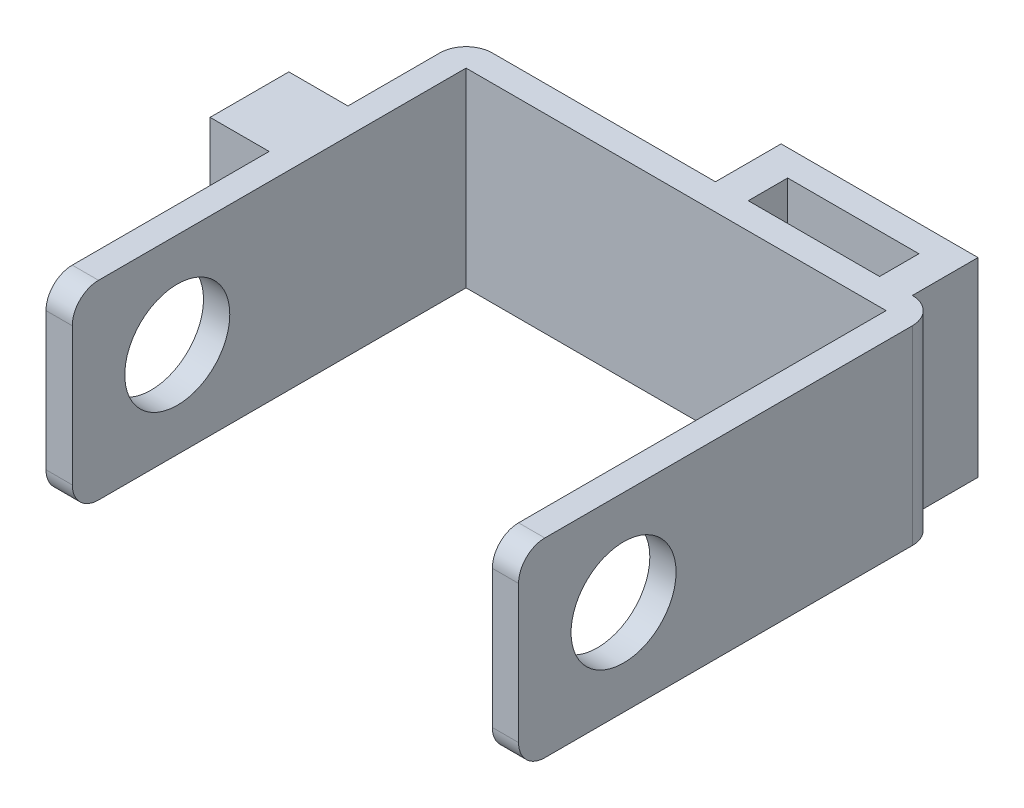
SolidWorks part; units mm, degrees
ref_plane "Спереди" through (0, 0, 0) normal (0, 0, 1) x (1, 0, 0)
ref_plane "Сверху" through (0, 0, 0) normal (0, 1, 0) x (1, 0, 0)
ref_plane "Справа" through (0, 0, 0) normal (1, 0, 0) x (0, 0, -1)
sketch "Эскиз1" plane through (0, 0, 0) normal (0, 1, 0) x (1, 0, 0)
  line L0 (0, 0) -> (-2, 0)
  line L2 (0, 0) -> (0, 30)
  line L3 (0, 30) -> (32, 30)
  line L4 (32, 0) -> (32, 30)
  line L5 (-2, 0) -> (-2, 32)
  line L6 (-2, 32) -> (17, 32)
  line L7 (34, 32) -> (34, 0)
  line L8 (32, 0) -> (34, 0)
  line L11 (17, 32) -> (17, 37)
  line L12 (32, 32) -> (32, 37)
  line L13 (17, 37) -> (32, 37)
  line L14 (32, 32) -> (34, 32)
  dimension "D1" = 32
  dimension "D2" = 32
  dimension "D3" = 5
  dimension "D4" = 2
  dimension "D7" = 15
  dimension "D8" = 2
  dimension "D9" = 2
  dimension "D10" = 32
  dimension "D11" = 2
extrude "Бобышка-Вытянуть1" add sketch "Эскиз1" along normal blind 14.5 contours L2 L3 L4 L8 L7 L14 L12 L13 L11 L6 L5 L0
sketch "Эскиз2" plane through (0, 14.5, 0) normal (0, 1, 0) x (1, 0, 0)
  line L0 (17, 32) -> (17, 37) construction
  line L2 (19.5, 32) -> (29.5, 32)
  line L3 (19.5, 32) -> (19.5, 35)
  line L4 (19.5, 35) -> (29.5, 35)
  line L5 (29.5, 32) -> (29.5, 35)
  line L6 (32, 32) -> (34, 32) construction
  dimension "D1" = 10
  dimension "D2" = 3
  dimension "D3" = 2.5
extrude "Вырез-Вытянуть1" cut sketch "Эскиз2" against normal through all
sketch "Эскиз3" plane through (34, 0, 0) normal (1, 0, 0) x (0, 0, -1)
  line L0 (28.9485, 7.25) -> (-2.8395, 7.25) construction
  line L5 (30, 14.5) -> (30, 0) construction
  line L7 (32, 14.5) -> (32, 0) construction
  line L9 (0, 14.5) -> (0, 0) construction
  circle A0 centre (8, 7.25) radius 4
  point P0 (0, 7.25)
  point P6 (0, 7.25)
  dimension "D1" = 8
  dimension "D2" = 8
extrude "Вырез-Вытянуть3" cut sketch "Эскиз3" against normal blind 40 contours A0
fillet "Скругление1" radius 2 1 edges at (34, 7.25, -32)
fillet "Скругление2" radius 2 1 edges at (-2, 7.25, -32)
fillet "Скругление3" radius 2 1 edges at (-1, 14.5, 0)
fillet "Скругление4" radius 2 1 edges at (33, 14.5, 0)
fillet "Скругление5" radius 2 1 edges at (33, 0, 0)
fillet "Скругление6" radius 2 1 edges at (-1, 0, 0)
sketch "Эскиз5" plane through (-2, 0, 0) normal (-1, 0, 0) x (0, 0, 1)
  line L1 (-17, 14.5) -> (-17, 0)
  line L2 (-2, 14.5) -> (-30, 14.5) construction
  line L3 (-2, 0) -> (-30, 0) construction
  line L4 (-23, 14.5) -> (-23, 0)
  line L5 (-17, 14.5) -> (-23, 14.5)
  line L6 (-17, 0) -> (-23, 0)
  circle A4 centre (-8, 7.25) radius 4 construction
  point P0 (-8, 7.25)
  dimension "D1" = 9
  dimension "D2" = 6
extrude "Бобышка-Вытянуть2" add sketch "Эскиз5" along normal blind 4.5
sketch "Эскиз6" plane through (0, 0, -17) normal (0, 0, 1) x (1, 0, 0)
  line L0 (-2, 0) -> (-2, 14.5) construction
  line L1 (-2, 10.25) -> (-2, 4.25)
  line L2 (-2, 4.25) -> (-4.5, 4.25)
  line L3 (-4.5, 4.25) -> (-4.5, 10.25)
  line L4 (-4.5, 10.25) -> (-2, 10.25)
  point P0 (-2, 7.25)
  dimension "D1" = 6
  dimension "D2" = 2.5
extrude "Вырез-Вытянуть4" cut sketch "Эскиз6" against normal through all
